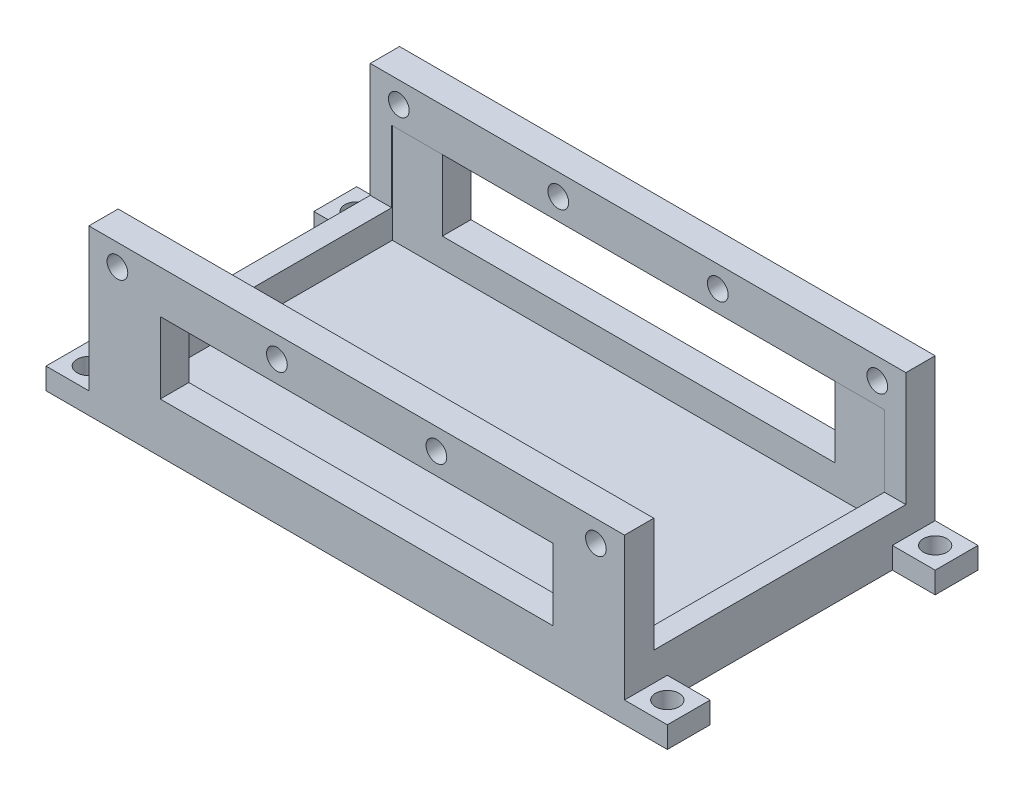
SolidWorks part; units mm, degrees
ref_plane "Front Plane" through (0, 0, 0) normal (0, 0, 1) x (1, 0, 0)
ref_plane "Top Plane" through (0, 0, 0) normal (0, 1, 0) x (1, 0, 0)
ref_plane "Right Plane" through (0, 0, 0) normal (1, 0, 0) x (0, 0, -1)
sketch "Sketch1" plane through (0, 0, 0) normal (0, 1, 0) x (1, 0, 0)
  line L0 (-34.5, -964.5) -> (-34.5, 49035.5) construction
  line L1 (0, 0) -> (-69, 0)
  line L2 (0, 0) -> (0, 35.5)
  line L3 (0, 35.5) -> (-69, 35.5)
  line L4 (-69, 0) -> (-69, 35.5)
  line L5 (-72, 39.5) -> (3, 39.5)
  line L6 (-72, 39.5) -> (-72, -4)
  line L7 (-72, -4) -> (3, -4)
  line L8 (3, 39.5) -> (3, -4)
  line L9 (-72, -4) -> (-78, -4)
  line L10 (-72, -4) -> (-72, 2)
  line L11 (-72, 2) -> (-78, 2)
  line L12 (-78, -4) -> (-78, 2)
  line L13 (-1071, 17.75) -> (48929, 17.75) construction
  line L14 (3, 2) -> (9, 2)
  line L15 (9, -4) -> (9, 2)
  line L16 (3, -4) -> (9, -4)
  line L17 (3, -4) -> (3, 2)
  line L18 (3, 39.5) -> (9, 39.5)
  line L19 (9, 39.5) -> (9, 33.5)
  line L20 (3, 33.5) -> (9, 33.5)
  line L21 (3, 39.5) -> (3, 33.5)
  line L22 (-72, 33.5) -> (-78, 33.5)
  line L23 (-78, 39.5) -> (-78, 33.5)
  line L24 (-72, 39.5) -> (-78, 39.5)
  line L25 (-72, 39.5) -> (-72, 33.5)
  circle A0 centre (-75, -1) radius 1.65
  circle A1 centre (6, -1) radius 1.65
  circle A2 centre (6, 36.5) radius 1.65
  circle A3 centre (-75, 36.5) radius 1.65
  point P15 (-75, 2)
  point P17 (-78, -1)
  point P21 (-34.5, 35.5)
  point P22 (-72, 17.75)
  dimension "D8" = 3.3
  dimension "D1" = 35.5
  dimension "D2" = 69
  dimension "D3" = 3
  dimension "D4" = 4
  dimension "D5" = 4
  dimension "D7" = 6
extrude "Boss-Extrude1" add sketch "Sketch1" along normal blind 3 contours L6 L24 L23 L22 A3 | L8 L5 L6 L7 L1 L4 L3 L2 | A0 | L8 L16 L15 L14 A1 | L8 L20 L19 L18 A2 | L9 L12 L11 L10 | L2 L1 L4 L3 region at (-34.5, 0, -38.633) region at (-72.0849, 0, -36.5) region at (6, 0, -39.4151) region at (6, 0, -1.9151) region at (-75, 0, 1)
sketch "Sketch2" plane through (0, 3, 0) normal (0, 1, 0) x (1, 0, 0)
  line L0 (3, 33.5) -> (3, 2) construction
  line L1 (-69, 35.5) -> (0, 35.5)
  line L2 (-69, 35.5) -> (-69, 0)
  line L3 (-69, 0) -> (0, 0)
  line L4 (0, 35.5) -> (0, 0)
  line L5 (-72, 33.5) -> (-72, 2) construction
  line L6 (9, 39.5) -> (-78, 39.5) construction
  line L7 (-78, -4) -> (9, -4) construction
  line L20 (-72, 33.5) -> (-72, 39.5)
  line L21 (-72, 2) -> (-72, -4)
  line L22 (3, 2) -> (3, -4)
  line L23 (3, 33.5) -> (3, 39.5)
  line L32 (-78, 33.5) -> (-72, 33.5)
  line L33 (-72, 33.5) -> (-72, 2)
  line L34 (-72, 2) -> (-78, 2)
  line L35 (-78, 2) -> (-78, -4)
  line L36 (-78, -4) -> (9, -4)
  line L37 (9, -4) -> (9, 2)
  line L38 (9, 2) -> (3, 2)
  line L39 (3, 2) -> (3, 33.5)
  line L40 (3, 33.5) -> (9, 33.5)
  line L41 (9, 33.5) -> (9, 39.5)
  line L42 (9, 39.5) -> (-78, 39.5)
  line L43 (-78, 39.5) -> (-78, 33.5)
  line L45 (-72, 33.5) -> (-72, 2)
  line L48 (-72, -4) -> (3, -4)
  line L49 (9, -4) -> (9, 2)
  line L51 (3, 2) -> (3, 33.5)
  line L53 (9, 33.5) -> (9, 39.5)
  line L54 (3, 39.5) -> (-72, 39.5)
  line M18 (-72, 33.5) -> (-72, 2)
  line M21 (-78, -4) -> (9, -4)
  line M24 (3, 2) -> (3, 33.5)
  line M27 (9, 39.5) -> (-78, 39.5)
  dimension "D1" = 3
  dimension "D2" = 3
  dimension "D3" = 4
  dimension "D4" = 4
  dimension "D5" = 0
extrude "Boss-Extrude2" add sketch "Sketch2" along normal blind 4 contours L23 L20 L21 L22 L1 L4 L3 L2 M24 M27 M18 M21 region at (-71.133, 3, -36.5)
sketch "Sketch3" plane through (0, 7, 0) normal (0, 1, 0) x (1, 0, 0)
  line L0 (0, 35.5) -> (0, 0) construction
  line L1 (-69, 0) -> (0, 0) construction
  line L2 (-69, 35.5) -> (-69, 0) construction
  line L3 (-69, 35.5) -> (0, 35.5) construction
  line L4 (3, -4) -> (3, 39.5)
  line L5 (3, 39.5) -> (-72, 39.5)
  line L6 (-72, 39.5) -> (-72, -4)
  line L7 (-72, -4) -> (3, -4)
  line L8 (3, -4) -> (3, 0.1)
  line L9 (3, 39.5) -> (-7, 39.5)
  line L10 (-72, 39.5) -> (-72, 35.4)
  line L11 (-72, -4) -> (-62, -4)
  line L12 (0, 35.5) -> (0, 35.4)
  line L13 (-69, 0) -> (-62, 0)
  line L14 (-69, 35.5) -> (-69, 35.4)
  line L15 (-69, 35.5) -> (-62, 35.5)
  line L16 (-69, 35.4) -> (-72, 35.4)
  line L17 (-62, 35.5) -> (-62, 39.5)
  line L18 (-34.5, -964.5) -> (-34.5, 49035.5) construction
  line L19 (-1071, 17.75) -> (48929, 17.75) construction
  line L20 (0, 35.4) -> (3, 35.4)
  line L21 (-7, 35.5) -> (-7, 39.5)
  line L22 (0, 0.1) -> (3, 0.1)
  line L23 (-7, 0) -> (-7, -4)
  line L24 (-62, 0) -> (-62, -4)
  line L25 (-69, 0.1) -> (-72, 0.1)
  line L26 (-72, 0.1) -> (-72, -4)
  line L27 (-69, 0.1) -> (-69, 0)
  line L28 (-7, 0) -> (0, 0)
  line L29 (-7, -4) -> (3, -4)
  line L30 (0, 0.1) -> (0, 0)
  line L31 (3, 35.4) -> (3, 39.5)
  line L32 (-7, 35.5) -> (0, 35.5)
  line L33 (-62, 39.5) -> (-72, 39.5)
  dimension "D2" = 10
  dimension "D3" = 4.1
  dimension "D1" = 0
extrude "Boss-Extrude3" add sketch "Sketch3" along normal blind 10
sketch "Sketch4" plane through (0, 17, 0) normal (0, 1, 0) x (1, 0, 0)
  line L1 (-72, 39.5) -> (3, 39.5)
  line L2 (-72, 39.5) -> (-72, 35.4)
  line L3 (-72, 35.4) -> (3, 35.4)
  line L4 (3, 39.5) -> (3, 35.4)
  line L5 (3, -4) -> (-72, -4)
  line L6 (3, -4) -> (3, 0.1)
  line L7 (3, 0.1) -> (-72, 0.1)
  line L8 (-72, -4) -> (-72, 0.1)
extrude "Boss-Extrude4" add sketch "Sketch4" along normal blind 6
sketch "Sketch5" plane through (0, 0, 4) normal (0, 0, 1) x (1, 0, 0)
  line L0 (-62, 17) -> (-62, 23) construction
  line L1 (-72, 23) -> (3, 23) construction
  line L2 (-72, 23) -> (-72, 3) construction
  line L3 (3, 23) -> (3, 3) construction
  circle A0 centre (-68, 20) radius 1.45
  circle A1 centre (-45.6667, 20) radius 1.45
  circle A2 centre (-23.3333, 20) radius 1.45
  circle A3 centre (-1, 20) radius 1.45
  point P8 (-62, 20)
  dimension "D1" = 2.9
  dimension "D2" = 4
  dimension "D4" = 4
  dimension "D3" = 4
extrude "Cut-Extrude1" cut sketch "Sketch5" against normal through all
